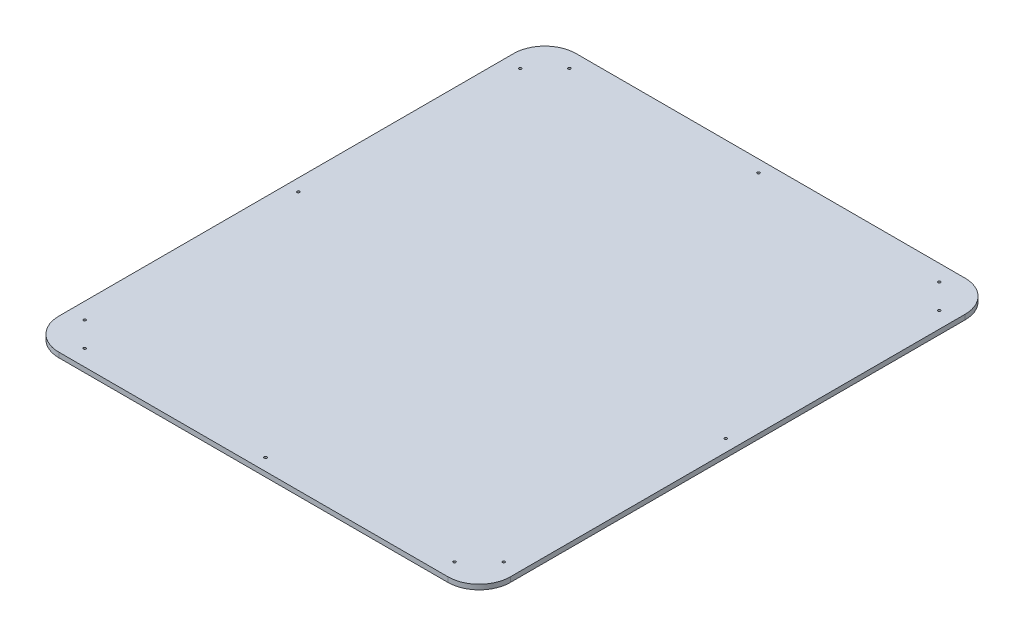
SolidWorks part; units mm, degrees
ref_plane "Alzado" through (0, 0, 0) normal (0, 0, 1) x (1, 0, 0)
ref_plane "Planta" through (0, 0, 0) normal (0, 1, 0) x (1, 0, 0)
ref_plane "Vista lateral" through (0, 0, 0) normal (1, 0, 0) x (0, 0, -1)
sketch "Croquis1" plane through (0, 0, 0) normal (0, 1, 0) x (1, 0, 0)
  line L1 (0, 0) -> (550, 0)
  line L2 (0, 0) -> (0, 630)
  line L3 (0, 630) -> (550, 630)
  line L4 (550, 0) -> (550, 630)
  dimension "D1" = 550
  dimension "D2" = 630
extrude "Saliente-Extruir1" add sketch "Croquis1" along normal blind 6
sketch "Croquis2" plane through (0, 6, 0) normal (0, 1, 0) x (1, 0, 0)
  line L0 (0, 630) -> (0, 0) construction
  line L1 (550, 630) -> (0, 630) construction
  line L2 (550, 315) -> (0, 315) construction
  line L3 (550, 0) -> (550, 630) construction
  line L4 (0, 0) -> (550, 0) construction
  line L5 (275, 630) -> (275, 0) construction
  line L6 (0, 630) -> (0, 0) construction
  circle A0 centre (19.75, 610.25) radius 4.05 construction
  circle A1 centre (19.75, 19.75) radius 4.05 construction
  circle A2 centre (530.25, 19.75) radius 4.05 construction
  circle A3 centre (530.25, 610.25) radius 4.05 construction
  circle A4 centre (500.25, 610.25) radius 1.55
  circle A6 centre (530.25, 580.25) radius 1.55
  circle A7 centre (530.25, 49.75) radius 1.55
  circle A8 centre (19.75, 580.25) radius 1.55
  circle A9 centre (19.75, 49.75) radius 1.55
  circle A17 centre (500.25, 19.75) radius 1.55
  circle A28 centre (49.75, 610.25) radius 1.55
  circle A35 centre (515.25, 595.25) radius 4.05 construction
  circle A36 centre (34.7523, 34.7523) radius 4.05 construction
  circle A37 centre (49.75, 19.75) radius 1.55
  circle A38 centre (34.75, 595.25) radius 4.05 construction
  circle A47 centre (515.2477, 34.7523) radius 4.05 construction
  dimension "D1" = 8.1
  dimension "D5" = 19.75
  dimension "D3" = 19.75
  dimension "D6" = 3.1
  dimension "D2" = 19.75
  dimension "D4" = 19.75
  dimension "D7" = 30
  dimension "D8" = 30
  dimension "D20" = 15
  dimension "D21" = 15
  dimension "D22" = 15.0023
  dimension "D23" = 15.0023
  dimension "D24" = 30
  dimension "D25" = 30
extrude "Cortar-Extruir1" cut sketch "Croquis2" against normal up to surface (6 mm away) up to face at (275, 0, -315)
fillet "Redondeo1" radius 38 4 edges at (0, 3, -630) (550, 3, -630) (550, 3, 0) (0, 3, 0)
sketch "Croquis3" plane through (0, 6, 0) normal (0, 1, 0) x (1, 0, 0)
  line L0 (275, 630) -> (275, 0) construction
  line L1 (512, 630) -> (38, 630) construction
  line L2 (38, 0) -> (512, 0) construction
  line L3 (0, 315) -> (550, 315) construction
  line L4 (0, 592) -> (0, 38) construction
  line L5 (550, 38) -> (550, 592) construction
  circle A0 centre (275, 615.25) radius 1.6
  circle A1 centre (14.75, 315) radius 1.6
  circle A2 centre (535.25, 315) radius 1.6
  circle A3 centre (275, 14.75) radius 1.6
  dimension "D1" = 3.2
  dimension "D3" = 3.2
  dimension "D5" = 3.2
  dimension "D7" = 3.2
  dimension "D2" = 14.75
  dimension "D4" = 14.75
  dimension "D6" = 14.75
  dimension "D8" = 14.75
extrude "Cortar-Extruir2" cut sketch "Croquis3" against normal up to surface (6 mm away) up to face at (530.25, 0, -51.3)
